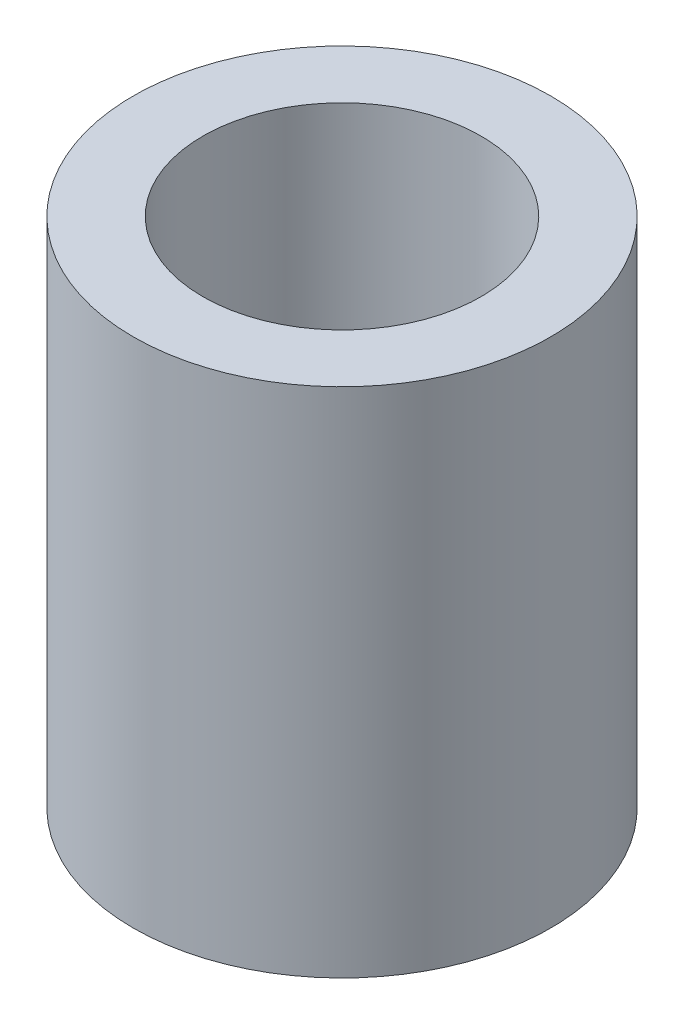
SolidWorks part; units mm, degrees
material "Nylon 101"
ref_plane "Front Plane" through (0, 0, 0) normal (0, 0, 1) x (1, 0, 0)
ref_plane "Top Plane" through (0, 0, 0) normal (0, 1, 0) x (1, 0, 0)
ref_plane "Right Plane" through (0, 0, 0) normal (1, 0, 0) x (0, 0, -1)
sketch "Sketch1" plane through (0, 0, 0) normal (0, 1, 0) x (1, 0, 0)
  circle A0 centre (0, 0) radius 3.175
  circle A1 centre (0, 0) radius 4.7625
  dimension "D1" = 6.35
  dimension "D2" = 9.525
extrude "Boss-Extrude1" add sketch "Sketch1" along normal blind 11.684
